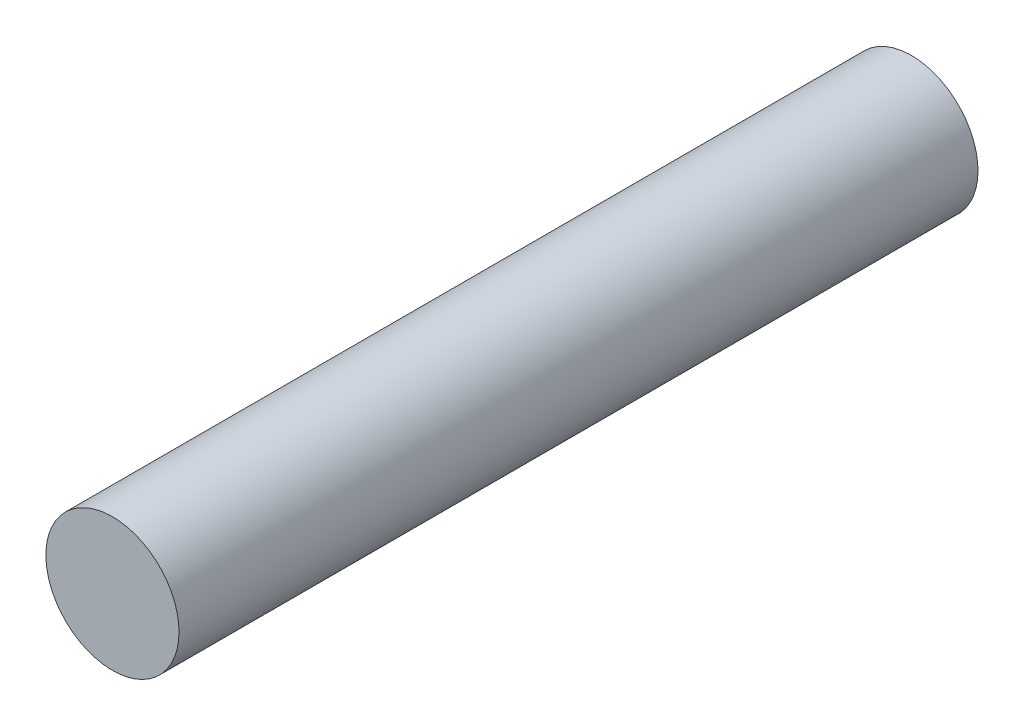
SolidWorks part; units mm, degrees
ref_plane "Front Plane" through (0, 0, 0) normal (0, 0, 1) x (1, 0, 0)
ref_plane "Top Plane" through (0, 0, 0) normal (0, 1, 0) x (1, 0, 0)
ref_plane "Right Plane" through (0, 0, 0) normal (1, 0, 0) x (0, 0, -1)
sketch "Sketch1" plane through (0, 0, 0) normal (0, 0, 1) x (1, 0, 0)
  circle A0 centre (0, 0) radius 1
  dimension "D1" = 2
extrude "Boss-Extrude1" add sketch "Sketch1" along normal blind 6 and the other way blind 6
